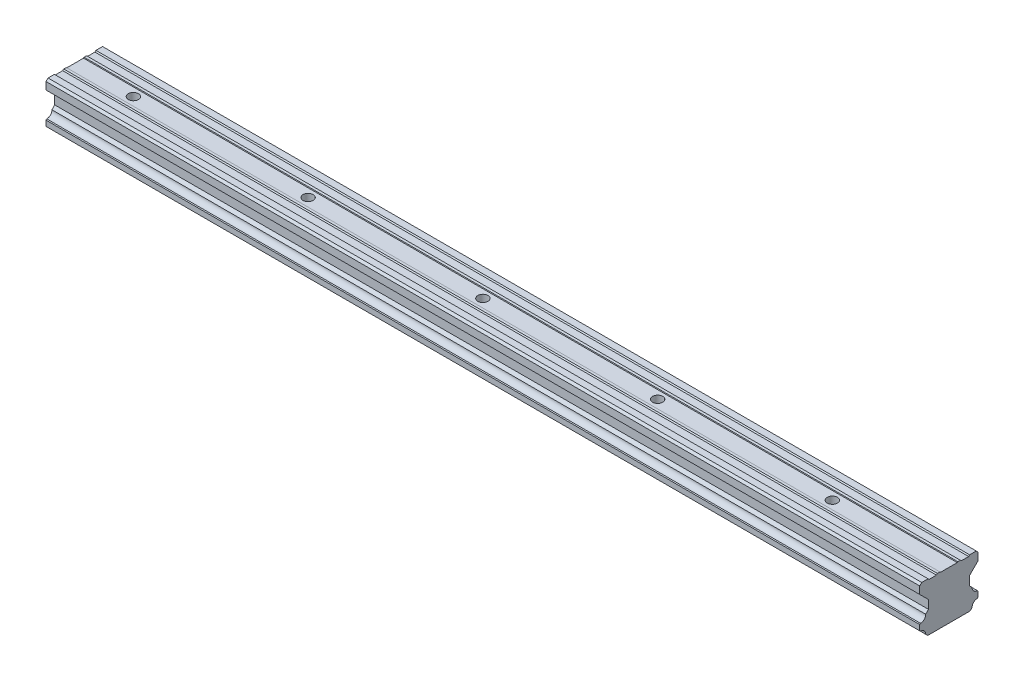
SolidWorks part; units mm, degrees
material "ASTM A36 Steel"
ref_plane "Front Plane" through (0, 0, 0) normal (0, 0, 1) x (1, 0, 0)
ref_plane "Top Plane" through (0, 0, 0) normal (0, 1, 0) x (1, 0, 0)
ref_plane "Right Plane" through (0, 0, 0) normal (1, 0, 0) x (0, 0, -1)
sketch "Sketch1" plane through (0, 0, 0) normal (1, 0, 0) x (0, 0, -1)
  line L0 (-7.9658, -7.694) -> (-7.2663, -8.3935)
  line L1 (-7.2663, -8.3935) -> (7.2663, -8.3935)
  line L2 (7.2663, -8.3935) -> (7.9658, -7.694)
  line L3 (9.7474, -5.9133) -> (10, -5.6608)
  line L4 (10, -5.6608) -> (10, -3.7884)
  line L5 (10, -3.7884) -> (9.7474, -3.5358)
  line L6 (7.9658, -1.7232) -> (7.0051, -0.7626)
  line L7 (7.0051, -0.7626) -> (7.0051, 2.1662)
  line L8 (7.0051, 2.1662) -> (10, 5.1611)
  line L9 (10, 5.1611) -> (10, 7.7124)
  line L10 (10, 7.7124) -> (9.4085, 8.3935)
  line L11 (9.4085, 8.3935) -> (7.133, 8.3935)
  line L12 (7.133, 8.3935) -> (6.7895, 8.05)
  line L13 (6.7895, 8.05) -> (4.2711, 8.05)
  line L14 (4.2711, 8.05) -> (3.9277, 8.3935)
  line L15 (3.9277, 8.3935) -> (3.0613, 8.3935)
  line L16 (3.0613, 8.3935) -> (2.872, 8.2042)
  line L17 (2.872, 8.2042) -> (-2.872, 8.2042)
  line L18 (-2.872, 8.2042) -> (-3.0613, 8.3935)
  line L19 (-3.0613, 8.3935) -> (-3.9277, 8.3935)
  line L20 (-3.9277, 8.3935) -> (-4.2712, 8.05)
  line L21 (-4.2712, 8.05) -> (-6.7895, 8.05)
  line L22 (-6.7895, 8.05) -> (-7.133, 8.3935)
  line L23 (-7.133, 8.3935) -> (-9.3077, 8.3935)
  line L24 (-9.3077, 8.3935) -> (-10, 7.7012)
  line L25 (-10, 7.7012) -> (-10, 5.1611)
  line L26 (-10, 5.1611) -> (-7.0051, 2.1662)
  line L27 (-7.0051, 2.1662) -> (-7.0051, -0.7626)
  line L28 (-7.0051, -0.7626) -> (-7.9658, -1.7232)
  line L29 (-9.7474, -5.9133) -> (-10, -5.6608)
  line L30 (-10, -5.6608) -> (-10, -3.7884)
  line L31 (-10, -3.7884) -> (-9.7474, -3.5358)
  arc A0 (-7.9658, -7.694) -> (-9.7474, -5.9133) centre (-9.7035, -7.6511) ccw
  arc A1 (-9.7474, -3.5358) -> (-7.9658, -1.7232) centre (-9.7025, -1.7981) ccw
  arc A2 (7.9658, -1.7232) -> (9.7474, -3.5358) centre (9.7025, -1.7981) ccw
  arc A3 (9.7474, -5.9133) -> (7.9658, -7.694) centre (9.7035, -7.6511) ccw
extrude "Boss-Extrude1" add sketch "Sketch1" along normal blind 300
sketch "Sketch2" plane through (0, -8.3935, 0) normal (0, -1, 0) x (1, 0, 0)
  circle A0 centre (20, 0) radius 3
  dimension "D1" = 6
  dimension "D2" = 20
hole_wizard "Hole1" positions "3DSketch1" profile "Sketch3" legacy end condition through all
sketch3d "3DSketch1"
  point P0 (20, -8.3935, 0)
sketch "Sketch3" plane through (20, -8.3935, 0) normal (1, 0, 0) x (0, 0, -1)
  line L0 (0, 0) -> (0, 16.7869)
  line L1 (0, 16.7869) -> (1.75, 16.7869)
  line L2 (1.75, 16.7869) -> (1.75, 8.5)
  line L3 (1.75, 8.5) -> (3, 8.5)
  line L4 (3, 8.5) -> (3, 0)
  line L5 (3, 0) -> (0, 0)
  line L6 (0, 110) -> (0, -10) construction
  dimension "Diameter" = 3.5
  dimension "Depth" = 16.7869
  dimension "C-Bore Diameter" = 6
  dimension "C-Bore Depth" = 8.5
sketch "Sketch4" plane through (0, -8.3935, 0) normal (0, -1, 0) x (-1, 0, 0)
  line L0 (0, 0) -> (-300, 0) construction
  line L1 (-300, -7.2663) -> (-300, 7.2663) construction
pattern_linear "LPattern1" count 5 spacing 60 along (1, 0, 0) of "Hole1"
